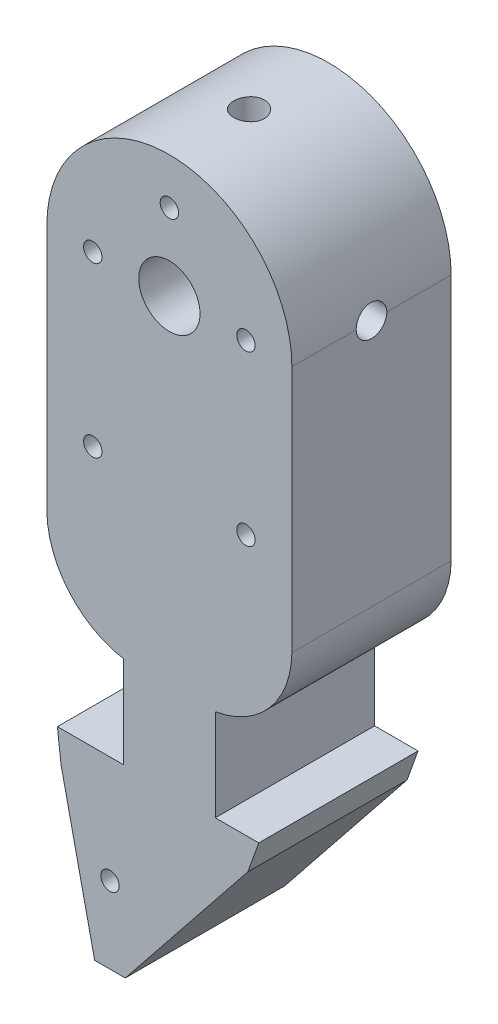
SolidWorks part; units mm, degrees
ref_plane "前视基准面" through (0, 0, 0) normal (0, 0, 1) x (1, 0, 0)
ref_plane "上视基准面" through (0, 0, 0) normal (0, 1, 0) x (1, 0, 0)
ref_plane "右视基准面" through (0, 0, 0) normal (1, 0, 0) x (0, 0, -1)
sketch "草图1" plane through (0, 0, 0) normal (0, 0, 1) x (1, 0, 0)
  line L0 (0, -55) -> (0, -75) construction
  line L1 (-20, 0) -> (20, 0)
  line L2 (-20, 0) -> (-20, -55)
  line L3 (-20, -55) -> (20, -55)
  line L4 (20, 0) -> (20, -55)
  line L5 (-20, 0) -> (20, -55) construction
  line L6 (-20, -55) -> (20, 0) construction
  line L7 (0, -75) -> (0, -100) construction
  line L8 (0, -75) -> (71.3073, -75) construction
  line L9 (0, -100) -> (73.1289, -100) construction
  line L10 (20, -55) -> (12.8, -75)
  line L11 (12.8, -75) -> (-7.2, -100)
  line L13 (12.2, -100) -> (37.7598, -100) construction
  line L14 (-12.2, -100) -> (0, -100)
  line L15 (-20, -55) -> (-17.7, -75)
  line L16 (-17.7, -75) -> (-12.2, -100)
  circle A0 centre (0, 0) radius 20
  point P7 (0, -27.5)
  dimension "D1" = 40
  dimension "D2" = 55
  dimension "D3" = 20
  dimension "D4" = 25
  dimension "D5" = 2.3
  dimension "D6" = 5.5
  dimension "D7" = 20
  dimension "D8" = 5
  dimension "D9" = 25
extrude "凸台-拉伸1" add sketch "草图1" along normal blind 26 contours L1 A0 | L1 A0 | A0 L2 L3 L4 | L15 L16 L14 L3 region at (0, 8.4883, 0) region at (0, -35.1004, 0) region at (0, -8.4883, 0) region at (-2.7295, -72.2597, 0)
sketch "草图2" plane through (0, 0, 26) normal (0, 0, 1) x (1, 0, 0)
  circle A0 centre (0, 0) radius 5
  dimension "D1" = 10
extrude "切除-拉伸1" cut sketch "草图2" against normal up to surface (26 mm away) up to face at (-3.0375, -55, 0)
sketch "草图5" plane through (-20, 0, 0) normal (-1, 0, 0) x (0, 0, 1)
  line L0 (13, 0) -> (13, 30.2427) construction
  line L1 (26, 0) -> (0, 0) construction
  circle A0 centre (13, 0) radius 2.5
  dimension "D1" = 5
extrude "切除-拉伸3" cut sketch "草图5" against normal blind 12
sketch "草图6" plane through (20, 0, 0) normal (1, 0, 0) x (0, 0, -1)
  circle A0 centre (-13, 0) radius 2.5 construction
  circle A1 centre (-13, 0) radius 2.5
extrude "切除-拉伸4" cut sketch "草图6" against normal blind 12
sketch "草图7" plane through (8, 0, 0) normal (1, 0, 0) x (0, 0, -1)
  circle A0 centre (-13, 0) radius 1.5
  dimension "D1" = 3
extrude "切除-拉伸5" cut sketch "草图7" against normal up to surface (16 mm away) up to face at (-8, -2.5, 13)
ref_plane "基准面1" through (0, 0, 0) normal (0, 1, 0) x (1, 0, 0)
sketch "草图8" plane through (0, 0, 0) normal (0, 1, 0) x (1, 0, 0)
  line L0 (0, 0) -> (0, -26) construction
  line L1 (-20, -26) -> (20, -26) construction
  circle A0 centre (0, -13) radius 1.5
  dimension "D1" = 3
extrude "切除-拉伸6" cut sketch "草图8" along normal up to surface (20 mm away) up to face at (0, 5.6211, 13)
ref_plane "基准面2" through (0, 20, 0) normal (0, 1, 0) x (1, 0, 0)
sketch "草图10" plane through (0, 20, 0) normal (0, 1, 0) x (1, 0, 0)
  circle A0 centre (0, -13) radius 2.5
  dimension "D1" = 5
extrude "切除-拉伸7" cut sketch "草图10" against normal blind 12
sketch "草图11" plane through (0, 0, 26) normal (0, 0, 1) x (1, 0, 0)
  line L0 (0, -55) -> (0, -70) construction
  line L1 (-20, -55) -> (20, -55)
  line L2 (-20, -55) -> (-20, -70)
  line L3 (-20, -70) -> (20, -70)
  line L4 (20, -55) -> (20, -70)
  line L6 (-7.5, -70) -> (7.5, -70)
  line L7 (-7.5, -70) -> (-7.5, -55)
  line L8 (-7.5, -55) -> (7.5, -55)
  line L9 (7.5, -70) -> (7.5, -55)
  line L10 (-7.5, -70) -> (7.5, -55) construction
  line L11 (-7.5, -55) -> (7.5, -70) construction
  point P8 (0, -62.5)
  line M10 (-20, -55) -> (-17.7, -75)
  line M14 (12.8, -75) -> (20, -55)
  dimension "D1" = 15
  dimension "D2" = 15
extrude "切除-拉伸8" cut sketch "草图11" against normal up to next contours L3 L7 L1 M10 | L9 L3 L1 M14 region at (-13.3294, -62.3147, 26) region at (12.524, -61.8112, 26)
sketch "草图12" plane through (0, 0, 26) normal (0, 0, 1) x (1, 0, 0)
  line L0 (-20, 0) -> (-20, -55) construction
  line L2 (0, 0) -> (0, -47.7697) construction
  line L3 (-20, -40) -> (-20, -55)
  line L4 (-20, -55) -> (-7.5, -55)
  line L5 (20, -55) -> (7.5, -55)
  line L6 (20, -40) -> (20, -55)
  arc A0 (-7.5, -55) -> (-20, -40) centre (-5.0015, -40.2096) cw
  arc A1 (7.5, -55) -> (20, -40) centre (5.0015, -40.2096) ccw
  line M10 (7.5, -55) -> (20, -55)
  line M11 (20, -55) -> (20, 0)
  line M14 (-20, -55) -> (-7.5, -55)
  dimension "D1" = 15
  dimension "D2" = 15
extrude "切除-拉伸9" cut sketch "草图12" against normal up to next contours A0 L3 M14 | A1 M10 M11 region at (-16.8539, -51.6614, 26) region at (16.8539, -51.6614, 26)
sketch "草图13" plane through (0, 0, 26) normal (0, 0, 1) x (1, 0, 0)
  circle A0 centre (-12.5, -27.5) radius 1.5 construction
  circle A1 centre (-12.5, -27.5) radius 1.5
  circle A2 centre (12.5, -27.5) radius 1.5 construction
  circle A3 centre (12.5, -27.5) radius 1.5
  circle A4 centre (12.5, 0) radius 1.5 construction
  circle A5 centre (12.5, 0) radius 1.5
  circle A6 centre (0, 12.5) radius 1.5 construction
  circle A7 centre (0, 12.5) radius 1.5
  circle A8 centre (-12.5, 0) radius 1.5 construction
  circle A9 centre (-12.5, 0) radius 1.5
  circle A10 centre (-9.7, -87.5) radius 1.5 construction
  circle A11 centre (-9.7, -87.5) radius 1.5
extrude "切除-拉伸10" cut sketch "草图13" against normal blind 5
sketch "草图14" plane through (0, 0, 0) normal (0, 0, -1) x (-1, 0, 0)
  circle A1 centre (12.5, 0) radius 1.5
  circle A2 centre (12.5, 0) radius 1.5
  circle A3 centre (0, 12.5) radius 1.5
  circle A4 centre (0, 12.5) radius 1.5
  circle A5 centre (-12.5, 0) radius 1.5
  circle A6 centre (-12.5, 0) radius 1.5
  circle A7 centre (-12.5, -27.5) radius 1.5
  circle A8 centre (-12.5, -27.5) radius 1.5
  circle A9 centre (12.5, -27.5) radius 1.5
  circle A10 centre (12.5, -27.5) radius 1.5
  circle A11 centre (9.7, -87.5) radius 1.5
  circle A12 centre (9.7, -87.5) radius 1.5
  dimension "D1" = 0
  dimension "D2" = 0
  dimension "D3" = 0
  dimension "D4" = 0
  dimension "D5" = 0
  dimension "D6" = 0
extrude "切除-拉伸11" cut sketch "草图14" against normal blind 5
